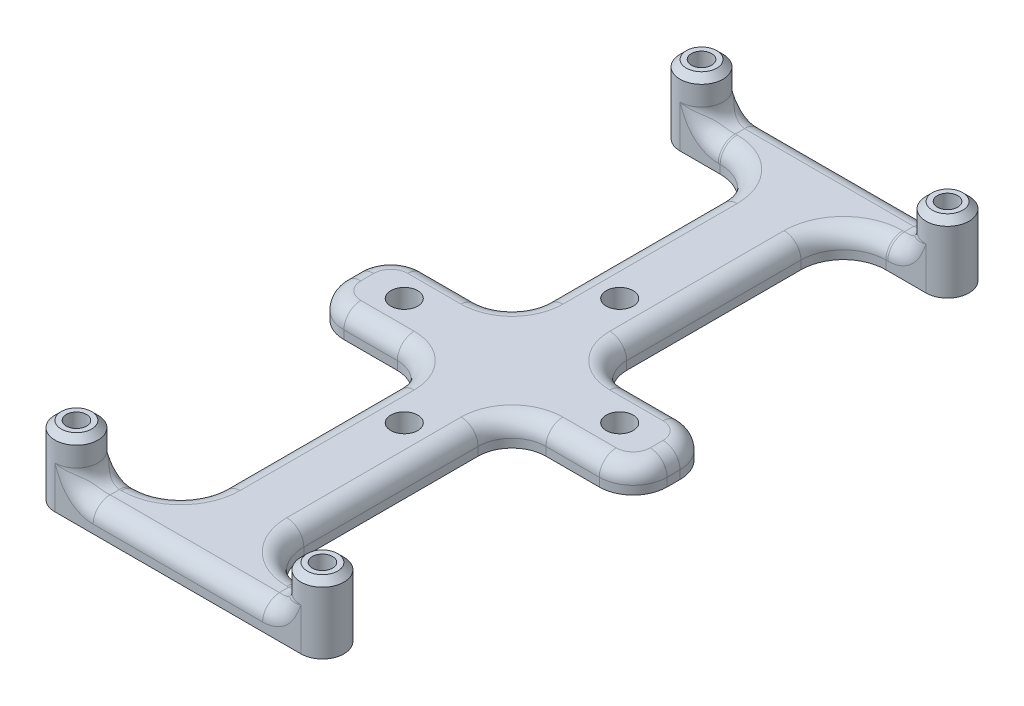
SolidWorks part; units mm, degrees
ref_plane "Front Plane" through (0, 0, 0) normal (0, 0, 1) x (1, 0, 0)
ref_plane "Top Plane" through (0, 0, 0) normal (0, 1, 0) x (1, 0, 0)
ref_plane "Right Plane" through (0, 0, 0) normal (1, 0, 0) x (0, 0, -1)
sketch "Sketch1" plane through (0, 0, 0) normal (0, 1, 0) x (1, 0, 0)
  line L1 (-4.7625, -34.305) -> (4.7625, -34.305)
  line L2 (-4.7625, -34.305) -> (-4.7625, 34.305)
  line L3 (-4.7625, 34.305) -> (4.7625, 34.305)
  line L4 (4.7625, -34.305) -> (4.7625, 34.305)
  line L5 (-4.7625, -34.305) -> (4.7625, 34.305) construction
  line L6 (-4.7625, 34.305) -> (4.7625, -34.305) construction
  line L7 (-14.5, 39.385) -> (14.5, 39.385)
  line L9 (-14.5, 34.305) -> (14.5, 34.305)
  line L11 (-14.5, 39.385) -> (14.5, 34.305) construction
  line L12 (-14.5, 34.305) -> (14.5, 39.385) construction
  line L13 (-14.5, -39.385) -> (14.5, -39.385)
  line L15 (-14.5, -34.305) -> (14.5, -34.305)
  line L17 (-14.5, -39.385) -> (14.5, -34.305) construction
  line L18 (-14.5, -34.305) -> (14.5, -39.385) construction
  arc A2 (-14.5, 34.305) -> (-14.5, 39.385) centre (-14.5, 36.845) cw
  arc A3 (14.5, 34.305) -> (14.5, 39.385) centre (14.5, 36.845) ccw
  arc A4 (-14.5, -39.385) -> (-14.5, -34.305) centre (-14.5, -36.845) cw
  arc A5 (14.5, -39.385) -> (14.5, -34.305) centre (14.5, -36.845) ccw
  point P0 (0, 0)
  point P6 (0, 36.845)
  point P11 (0, -36.845)
  dimension "D4" = 29
  dimension "D1" = 9.525
  dimension "D2" = 5.08
  dimension "D3" = 5.08
  dimension "D5" = 73.69
extrude "Boss-Extrude1" add sketch "Sketch1" along normal blind 3 contours L13 A5 L15 L1 A4 | L1 L4 L3 L2 | L9 A3 L7 A2 L3 region at (0, 0, 0) region at (0, 0, 36.845) region at (0, 0, -36.845)
sketch "Sketch2" plane through (0, 3, 0) normal (0, 1, 0) x (1, 0, 0)
  line L0 (0, 12.7) -> (0, -12.7) construction
  circle A0 centre (0, 12.7) radius 1.5875
  circle A1 centre (0, -12.7) radius 1.5875
  dimension "D2" = 3.175
  dimension "D3" = 3.175
  dimension "D1" = 25.4
extrude "Cut-Extrude1" cut sketch "Sketch2" against normal through all
sketch "Sketch3" plane through (0, 3, 0) normal (0, 1, 0) x (1, 0, 0)
  circle A0 centre (-14.5, 36.845) radius 2.54
  circle A1 centre (14.5, 36.845) radius 2.54
  circle A2 centre (14.5, -36.845) radius 2.54
  circle A3 centre (-14.5, -36.845) radius 2.54
  arc A4 (-14.5, 39.385) -> (-14.5, 34.305) centre (-14.5, 36.845) ccw construction
  arc A5 (14.5, 34.305) -> (14.5, 39.385) centre (14.5, 36.845) ccw construction
  arc A6 (-14.5, -34.305) -> (-14.5, -39.385) centre (-14.5, -36.845) ccw construction
  arc A7 (14.5, -39.385) -> (14.5, -34.305) centre (14.5, -36.845) ccw construction
extrude "Boss-Extrude2" add sketch "Sketch3" along normal blind 5.08
sketch "Sketch4" plane through (0, 8.08, 0) normal (0, 1, 0) x (1, 0, 0)
  circle A0 centre (-14.5, 36.845) radius 1.1938
  circle A1 centre (14.5, 36.845) radius 1.1938
  circle A2 centre (14.5, -36.845) radius 1.1938
  circle A3 centre (-14.5, -36.845) radius 1.1938
  dimension "D1" = 2.3876
  dimension "D2" = 2.3876
  dimension "D3" = 2.3876
  dimension "D4" = 2.3876
extrude "Cut-Extrude2" cut sketch "Sketch4" against normal blind 3.2004
sketch "Sketch5" plane through (0, 4.8796, 0) normal (0, 1, 0) x (1, 0, 0)
  circle A0 centre (-14.5, 36.845) radius 0.875
  circle A1 centre (14.5, 36.845) radius 0.875
  circle A2 centre (14.5, -36.845) radius 0.875
  circle A3 centre (-14.5, -36.845) radius 0.875
  dimension "D1" = 1.75
  dimension "D2" = 1.75
  dimension "D3" = 1.75
  dimension "D4" = 1.75
extrude "Cut-Extrude3" cut sketch "Sketch5" against normal through all
chamfer "Chamfer1" distance 0.75 angle 45 4 edges at (-14.5, 8.08, -34.305) (14.5, 8.08, -34.305) (14.5, 8.08, 39.385) (-14.5, 8.08, 39.385)
fillet "Fillet1" radius 5 4 edges at (-4.7625, 1.5, -34.305) (4.7625, 1.5, -34.305) (-4.7625, 1.5, 34.305) (4.7625, 1.5, 34.305)
fillet "Fillet2" radius 2 4 edges at (-11.96, 3, 36.845) (11.96, 3, 36.845) (11.96, 3, -36.845) (-11.96, 3, -36.845)
sketch "Sketch6" plane through (0, 3, 0) normal (0, 1, 0) x (1, 0, 0)
  line L1 (-19.05, -4.7625) -> (19.05, -4.7625)
  line L2 (-19.05, -4.7625) -> (-19.05, 4.7625)
  line L3 (-19.05, 4.7625) -> (19.05, 4.7625)
  line L4 (19.05, -4.7625) -> (19.05, 4.7625)
  line L5 (-19.05, -4.7625) -> (19.05, 4.7625) construction
  line L6 (-19.05, 4.7625) -> (19.05, -4.7625) construction
  point P0 (0, 0)
  dimension "D1" = 9.525
  dimension "D2" = 38.1
extrude "Boss-Extrude3" add sketch "Sketch6" against normal up to surface (3 mm away) up to face at (-14.5, 0, 37.72)
fillet "Fillet3" radius 4 8 edges at (-4.7625, 1.5, -4.7625) (-19.05, 1.5, -4.7625) (-19.05, 1.5, 4.7625) (-4.7625, 1.5, 4.7625) (4.7625, 1.5, 4.7625) (4.7625, 1.5, -4.7625) (19.05, 1.5, 4.7625) (19.05, 1.5, -4.7625)
sketch "Sketch7" plane through (0, 3, 0) normal (0, 1, 0) x (1, 0, 0)
  line L0 (-12.7, 0) -> (12.7, 0) construction
  circle A0 centre (-12.7, 0) radius 1.5875
  circle A1 centre (12.7, 0) radius 1.5875
  dimension "D2" = 3.175
  dimension "D3" = 3.175
  dimension "D1" = 25.4
extrude "Cut-Extrude4" cut sketch "Sketch7" against normal through all
fillet "Fillet4" radius 2 30 edges at (11.737, 3.1613, 34.305) (10.2498, 3, 34.305) (6.227, 3, 32.8405) (4.7625, 3, 19.0337) (11.737, 3.1613, -34.305) (10.2498, 3, -34.305) (6.227, 3, -32.8405) (4.7625, 3, -19.0337) (5.9341, 3, -5.9341) (11.9062, 3, -4.7625) (17.8784, 3, -3.5909) (19.05, 3, 0) (17.8784, 3, 3.5909) (11.9062, 3, 4.7625) (-11.737, 3.1613, 34.305) (-10.2498, 3, 34.305) (-6.227, 3, 32.8405) (-11.737, 3.1613, -34.305) (-10.2498, 3, -34.305) (-6.227, 3, -32.8405) (-4.7625, 3, -19.0337) (-5.9341, 3, -5.9341) (-11.9063, 3, -4.7625) (-17.8784, 3, -3.5909) (-19.05, 3, 0) (-17.8784, 3, 3.5909) (-11.9063, 3, 4.7625) (-5.9341, 3, 5.9341) (5.9341, 3, 5.9341) (-4.7625, 3, 19.0337)
fillet "Fillet5" radius 2 6 edges at (-11.737, 3.1613, -39.385) (11.737, 3.1613, -39.385) (-11.737, 3.1613, 39.385) (11.737, 3.1613, 39.385) (0, 3, -39.385) (0, 3, 39.385)
